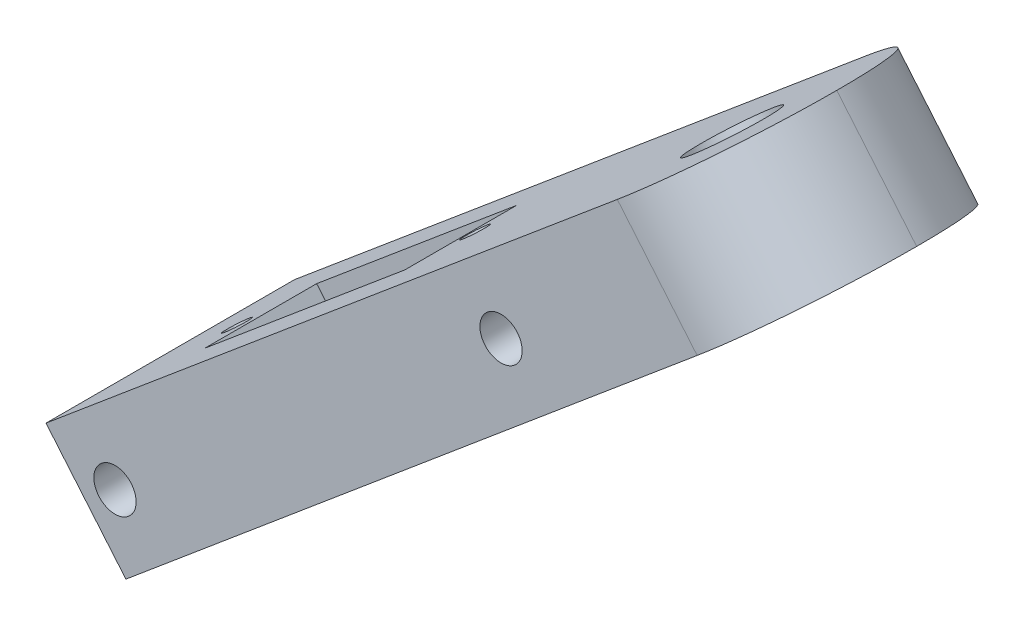
SolidWorks part; units mm, degrees
ref_plane "前视基准面" through (0, 0, 0) normal (0, 0, 1) x (1, 0, 0)
ref_plane "上视基准面" through (0, 0, 0) normal (0, 1, 0) x (1, 0, 0)
ref_plane "右视基准面" through (0, 0, 0) normal (1, 0, 0) x (0, 0, -1)
ref_axis "基准轴2" through (0, 0, -88.99) along (0, 0, 1)
ref_plane "基准面1" through (0, 0, 0) normal (-0.6428, 0.766, 0) x (0, 0, 1)
sketch "草图1" plane through (0, 0, 0) normal (-0.6428, 0.766, 0) x (0.766, 0.6428, 0)
  line L1 (10.5, 4.5) -> (-10.5, 4.5)
  line L2 (10.5, 4.5) -> (10.5, -4.5)
  line L3 (10.5, -4.5) -> (-10.5, -4.5)
  line L4 (-10.5, 4.5) -> (-10.5, -4.5)
  line L5 (10.5, 4.5) -> (-10.5, -4.5) construction
  line L6 (10.5, -4.5) -> (-10.5, 4.5) construction
  line L11 (-20, 10) -> (50, 10)
  line L12 (-20, 10) -> (-20, -10)
  line L13 (-20, -10) -> (50, -10)
  line L14 (50, 10) -> (50, -10)
  point P0 (0, 0)
  point P6 (0, 0)
extrude "凸台-拉伸1" add sketch "草图1" along normal blind 10
sketch "草图3" plane through (-6.4279, 7.6604, 0) normal (-0.6428, 0.766, 0) x (0.766, 0.6428, 0)
  circle A0 centre (39, 0) radius 3.3
  circle A1 centre (-13, 0) radius 1
  circle A2 centre (12, 0) radius 1
extrude "切除-拉伸1" cut sketch "草图3" against normal up to next
sketch "草图4" plane through (0, 0, 10) normal (0, 0, 1) x (1, 0, 0)
  line L0 (-18.5348, -9.0255) -> (35.0883, 35.9696) construction
  line L1 (-21.7488, -5.1953) -> (-15.3209, -12.8558) construction
  line L2 (31.8743, 39.7998) -> (38.3022, 32.1394) construction
  circle A0 centre (-16.1982, -7.0649) radius 1.7
  circle A1 centre (14.8626, 18.9983) radius 1.7
extrude "切除-拉伸2" cut sketch "草图4" against normal up to next
fillet "圆角1" radius 10 2 edges at (35.0883, 35.9696, -10) (35.0883, 35.9696, 10)
